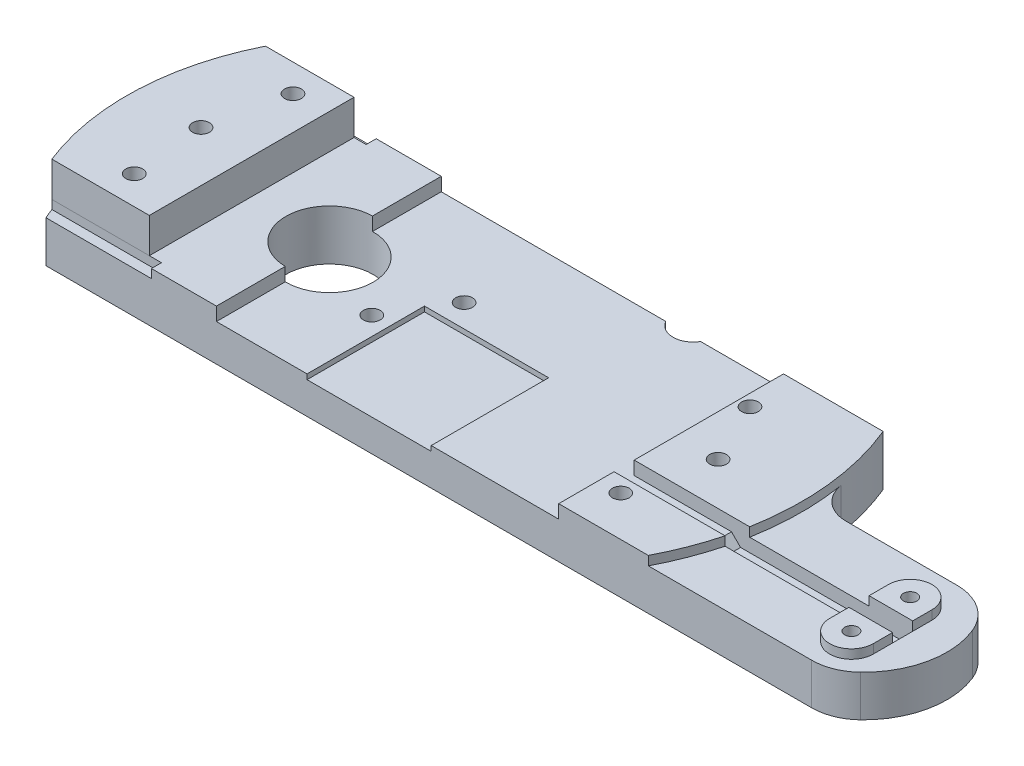
SolidWorks part; units mm, degrees
ref_plane "Front Plane" through (0, 0, 0) normal (0, 0, 1) x (1, 0, 0)
ref_plane "Top Plane" through (0, 0, 0) normal (0, 1, 0) x (1, 0, 0)
ref_plane "Right Plane" through (0, 0, 0) normal (1, 0, 0) x (0, 0, -1)
sketch "Sketch1" plane through (0, 0, 0) normal (0, 1, 0) x (1, 0, 0)
  line L1 (-97.5, -33.5) -> (97.5, -33.5)
  line L2 (-97.5, -33.5) -> (-97.5, 33.5)
  line L3 (-97.5, 33.5) -> (97.5, 33.5)
  line L4 (97.5, -33.5) -> (97.5, 33.5)
  line L5 (-97.5, -33.5) -> (97.5, 33.5) construction
  line L6 (-97.5, 33.5) -> (97.5, -33.5) construction
  point P0 (0, 0)
  dimension "D1" = 67
  dimension "D2" = 195
extrude "Boss-Extrude1" add sketch "Sketch1" along normal blind 25.4
sketch "Sketch2" plane through (0, 0, 0) normal (0, -1, 0) x (1, 0, 0)
  line L0 (-97.5, -33.5) -> (-97.5, 33.5) construction
  line L1 (97.5, 33.5) -> (97.5, -33.5) construction
  line L2 (97.5, 33.5) -> (88.5, 33.5)
  line L3 (-97.5, 33.5) -> (97.5, 33.5) construction
  line L4 (97.5, -33.5) -> (91.5, -33.5)
  line L5 (97.5, -33.5) -> (-97.5, -33.5) construction
  line L6 (-97.5, 33.5) -> (-91, 33.5)
  line L7 (-97.5, -33.5) -> (-88, -33.5)
  circle A0 centre (18.0922, -3.2198) radius 79.4078
  circle A1 centre (-22.6589, 2.9929) radius 74.8411
  line M7 (97.5, -33.5) -> (97.5, 33.5)
  line M8 (97.5, 33.5) -> (-97.5, 33.5)
  line M9 (-97.5, 33.5) -> (-97.5, -33.5)
  line M10 (-97.5, -33.5) -> (97.5, -33.5)
  dimension "D1" = 9
  dimension "D2" = 6
  dimension "D3" = 6.5
  dimension "D4" = 9.5
extrude "Cut-Extrude1" cut sketch "Sketch2" against normal through all contours A0 M7 M8 | A0 M10 M7 | A1 M9 M10 | A1 M8 M9 region at (94.8284, 0, 24.4273) region at (95.7123, 0, -25.9883) region at (-95.5654, 0, 25.941) region at (-94.6839, 0, -24.4966)
sketch "Sketch3" plane through (0, 0, 33.5) normal (0, 0, -1) x (-1, 0, 0)
  line L0 (97.5, 25.4) -> (63.2, 25.4)
  line L2 (63.2, 25.4) -> (63.2, 15)
  line L3 (63.2, 15) -> (40.2, 15)
  line L4 (40.2, 15) -> (40.2, 11)
  line L5 (40.2, 11) -> (-61.8, 11)
  line L6 (-91.5, 25.4) -> (88, 25.4) construction
  line L10 (97.5, 0) -> (97.5, 25.4) construction
  line L11 (-61.8, 11) -> (-61.8, 15)
  line L12 (-61.8, 15) -> (-97.5, 15)
  line L13 (-97.5, 25.4) -> (-97.5, 0) construction
  line L14 (-97.5, 15) -> (-97.5, 25.4)
  line L15 (-97.5, 25.4) -> (63.2, 25.4)
  line M13 (-88.5, 0) -> (-88.5, 25.4)
  line M14 (-88.5, 25.4) -> (91, 25.4)
  dimension "D1" = 10.4
  dimension "D2" = 34.3
  dimension "D3" = 23
  dimension "D4" = 4
  dimension "D5" = 102
extrude "Cut-Extrude2" cut sketch "Sketch3" along normal through all contours L11 L12 L2 L3 L4 L5 M13 M14 | L2 L3 L4 L5 L11 L12 L14 L15 region at (12.2699, 18.7206, 33.5)
sketch "Sketch4" plane through (0, 25.4, 0) normal (0, 1, 0) x (1, 0, 0)
  line L0 (-59.5873, 33.5) -> (-59.5873, 30.5)
  line L1 (-63.2, 33.5) -> (-88, 33.5) construction
  line L2 (-59.5873, 30.5) -> (-89.5873, 30.5)
  line L3 (-59.5873, -33.5) -> (-59.5873, -30.5)
  line L4 (-91, -33.5) -> (-63.2, -33.5) construction
  line L5 (-59.5873, -30.5) -> (-92.2617, -30.5)
  line L6 (-59.5873, 33.5) -> (-63.2, 33.5)
  line L7 (-59.5873, -33.5) -> (-63.2, -33.5)
  arc A0 (-88, 33.5) -> (-91, -33.5) centre (-22.6589, -2.9929) ccw construction
  line M5 (-91, -33.5) -> (-63.2, -33.5)
  line M6 (-63.2, -33.5) -> (-63.2, 33.5)
  line M7 (-63.2, 33.5) -> (-88, 33.5)
  arc M8 (-88, 33.5) -> (-91, -33.5) centre (-22.6589, -2.9929) ccw
  dimension "D1" = 3
  dimension "D2" = 3
  dimension "D3" = 30
extrude "Cut-Extrude3" cut sketch "Sketch4" against normal blind 13 contours L2 M6 M7 M8 | L0 L6 L2 M6 | L5 M6 M8 M5 | L7 L3 L5 M6 region at (-61.3937, 25.4, -32) region at (-76.0082, 25.4, -31.9845) region at (-77.4242, 25.4, 31.9889) region at (-61.3937, 25.4, 32)
sketch "Sketch6" plane through (0, 0, 0) normal (0, -1, 0) x (1, 0, 0)
  line L0 (-63.2, -33.5) -> (-97.5, -33.5)
  line L1 (91.5, -33.5) -> (-88, -33.5) construction
  line L2 (-63.2, -33.5) -> (-63.2, 33.5)
  line L3 (-91, 33.5) -> (88.5, 33.5) construction
  line L4 (-63.2, -9) -> (-28.1, -9) construction
  line L5 (-63.2, 8.7) -> (-18.7, 8.7) construction
  line L6 (-63.2, -8.3) -> (-8.2, -8.3) construction
  line L8 (91.5, -33.5) -> (-88, -33.5) construction
  line L9 (-97.5, -33.5) -> (-97.5, 33.5)
  line L10 (-97.5, 33.5) -> (-63.2, 33.5)
  circle A1 centre (-18.7, 8.7) radius 2.5
  circle A2 centre (74.1, -1.7) radius 2.5
  circle A3 centre (68.3, 21.5) radius 2.5
  circle A4 centre (65.3, -20) radius 2.5
  circle A5 centre (-8.2, -8.3) radius 2.5
  circle A6 centre (-76.2, 22) radius 2.5
  circle A7 centre (-78.2, 0.1) radius 2.5
  circle A8 centre (-73.2, -22.3) radius 2.5
  arc A10 (-91, 33.5) -> (-88, -33.5) centre (-22.6589, 2.9929) ccw construction
  dimension "D22" = 5
  dimension "D3" = 35.1
  dimension "D4" = 34.3
  dimension "D5" = 44.5
  dimension "D6" = 24.5
  dimension "D7" = 55
  dimension "D8" = 42.2
  dimension "D9" = 137.3
  dimension "D10" = 128.5
  dimension "D11" = 131.5
  dimension "D12" = 10
  dimension "D13" = 15
  dimension "D14" = 13
  dimension "D15" = 11.2
  dimension "D16" = 33.6
  dimension "D17" = 55.5
  dimension "D18" = 31.8
  dimension "D19" = 55
  dimension "D20" = 13.5
  dimension "D21" = 25.2
extrude "Cut-Extrude4" cut sketch "Sketch6" against normal through all contours A5 | A1 | A6 | A7 | A8 | A4 | A2 | A3 region at (-18.7, 0, 8.7) region at (74.1, 0, -1.7) region at (68.3, 0, 21.5) region at (65.3, 0, -20) region at (-8.2, 0, -8.3) region at (-76.2, 0, 22) region at (-78.2, 0, 0.1) region at (-73.2, 0, -22.3)
sketch "Sketch7" plane through (0, 11, 0) normal (0, 1, 0) x (1, 0, 0)
  line L1 (-13.2, 1.5) -> (23.8, 1.5)
  line L2 (-13.2, 1.5) -> (-13.2, -33.5)
  line L3 (-13.2, -33.5) -> (23.8, -33.5)
  line L4 (23.8, 1.5) -> (23.8, -33.5)
  line L8 (-63.2, 30.5) -> (-63.2, -30.5) construction
  line L9 (-63.2, 30.5) -> (-63.2, -30.5) construction
  line L10 (-40.2, -33.5) -> (61.8, -33.5) construction
  dimension "D1" = 50
  dimension "D2" = 87
  dimension "D3" = 35
extrude "Cut-Extrude5" cut sketch "Sketch7" against normal blind 1.5
sketch "Sketch8" plane through (0, 25.4, 0) normal (0, 1, 0) x (1, 0, 0)
  line L0 (-59.5873, -33.5) -> (-97.5, -33.5)
  line L1 (-97.5, -33.5) -> (-97.5, 33.5)
  line L3 (-97.5, 33.5) -> (31.9, 33.5)
  line L6 (31.9, 36.5) -> (31.9, 30.5)
  line L7 (31.9, 33.5) -> (37.0962, 33.5)
  line L10 (-59.5873, 33.5) -> (-88, 33.5) construction
  line L11 (-40.2, 33.5) -> (61.8, 33.5) construction
  circle A1 centre (31.9, 36.5) radius 6
  arc A2 (-89.5873, 30.5) -> (-92.2617, -30.5) centre (-22.6589, -2.9929) ccw construction
  dimension "D1" = 12
  dimension "D2" = 129.4
extrude "Cut-Extrude6" cut sketch "Sketch8" against normal blind 18.5 contours L6 A1 L7 | L3 A1 L6 region at (29.8648, 25.4, -32.2699) region at (33.9352, 25.4, -32.2699)
sketch "Sketch9" plane through (0, 0, 0) normal (0, -1, 0) x (1, 0, 0)
  line L0 (88.5, 33.5) -> (137.2004, 33.5)
  line L1 (139.5727, -7.5) -> (97.3846, -7.5)
  arc A0 (153.4738, 1.8643) -> (147.5429, 29.3643) centre (130.3054, 11.2571) ccw
  arc A1 (91.5, -33.5) -> (88.5, 33.5) centre (18.0922, -3.2198) ccw construction
  arc A2 (142.3827, -10.6321) -> (147.5429, 29.3643) centre (130.3054, 11.2571) ccw construction
  arc A3 (147.5429, 29.3643) -> (137.2004, 33.5) centre (137.2004, 18.5) ccw
  arc A4 (147.5429, 29.3643) -> (137.9704, 33.4802) centre (137.2004, 18.5) ccw construction
  arc A5 (139.5727, -7.5) -> (153.4738, 1.8643) centre (139.5727, 7.5) ccw
  circle A6 centre (112.8181, -27.5) radius 16 construction
  circle A7 centre (103.4238, 59.4942) radius 16 construction
  circle A8 centre (112.8181, -27.5) radius 20 construction
  arc A9 (97.3846, -7.5) -> (88.5, 33.5) centre (18.0922, -3.2198) ccw
  circle A10 centre (138.3, 5.25) radius 2
  circle A11 centre (138.3, 22.75) radius 2
  circle A12 centre (138.3, 22.75) radius 2 construction
  circle A13 centre (138.3, 5.25) radius 2 construction
  dimension "D1" = 4
extrude "Boss-Extrude2" add sketch "Sketch9" against normal offset from surface (12.3 mm away) 1.3 up to face at (-16.2, 11, 8.7) offset beyond the face yes
fillet "Fillet1" radius 10 1 edges at (97.3846, 6.15, -7.5)
sketch "Sketch10" plane through (0, -3, 0) normal (0, -1, 0) x (1, 0, 0)
  circle A0 centre (-40.0178, 0) radius 13
  dimension "D1" = 26
extrude "Cut-Extrude7" cut sketch "Sketch10" against normal up to surface (18 mm away) up to face at (-55.6437, 15, 0)
sketch "Sketch11" plane through (0, 12.3, 0) normal (0, 1, 0) x (1, 0, 0)
  line L0 (138.3, -5.25) -> (138.3, -22.75) construction
  line L1 (144.8, -5.25) -> (144.8, -22.75)
  line L2 (131.8, -5.25) -> (131.8, -22.75)
  line L3 (131.8, -11) -> (144.8, -11)
  line L4 (131.8, -17) -> (144.8, -17)
  line L5 (131.8, -14) -> (144.8, -14) construction
  arc A0 (144.8, -5.25) -> (131.8, -5.25) centre (138.3, -5.25) ccw
  arc A1 (131.8, -22.75) -> (144.8, -22.75) centre (138.3, -22.75) ccw
  point P4 (138.3, -14)
  circle M15 centre (138.3, -22.75) radius 2
  circle M16 centre (138.3, -5.25) radius 2
  dimension "D1" = 13
  dimension "D2" = 6
extrude "Boss-Extrude3" add sketch "Sketch11" along normal up to surface (2.7 mm away) contours L1 A0 L2 L3 M16 | L2 A1 L1 L4 M15 region at (144.6214, 12.3, 8.125) region at (144.6214, 12.3, 19.875) up to face at (70.8, 15, 21.5)
split "Split1" bodies to split 113 resulting bodies 114 115 split by face at (-53.8367, 15, 0)
sketch "Sketch12" plane through (0, 0, 11) normal (0, 0, 1) x (1, 0, 0)
  line L0 (144.8, 15) -> (144.8, 8.3)
  line L1 (144.8, 8.3) -> (93.5, 8.3)
  line L3 (97.5, 12.3) -> (88.5, 12.3) construction
  line L4 (90.8, 11) -> (61.8, 11)
  line L5 (61.8, 11) -> (61.8, 15)
  line L6 (61.8, 15) -> (88.5, 15) construction
  line L7 (61.8, 15) -> (144.8, 15)
  line L10 (97.5, 12.3) -> (93.5, 12.3) construction
  line L12 (88.5, 12.3) -> (137.2004, 12.3) construction
  line L13 (93.5, 12.3) -> (93.5, 8.3) construction
  line L14 (61.8, 11) -> (61.8, 15) construction
  line L15 (23.8, 11) -> (61.8, 11) construction
  line L16 (93.5, 8.3) -> (90.8, 11)
  dimension "D1" = 45
extrude "Cut-Extrude8" cut sketch "Sketch12" along normal up to surface (6 mm away) up to face at (138.3, 13.65, 17)
